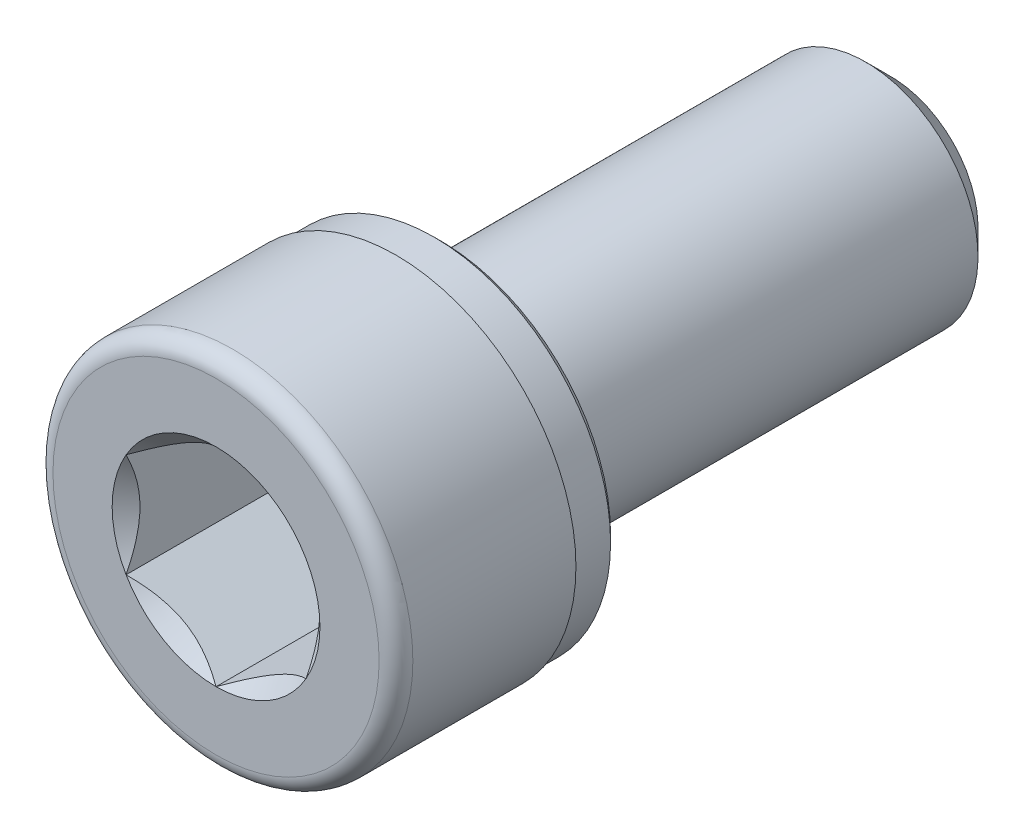
SolidWorks part; units mm, degrees
ref_plane "Front Plane" through (0, 0, 0) normal (0, 0, 1) x (1, 0, 0)
ref_plane "Top Plane" through (0, 0, 0) normal (0, 1, 0) x (1, 0, 0)
ref_plane "Right Plane" through (0, 0, 0) normal (1, 0, 0) x (0, 0, -1)
sketch "Sketch1" plane through (0, 0, 0) normal (1, 0, 0) x (0, 0, -1)
  line L0 (-15, 0) -> (15, 0) construction
  line L1 (15, 0) -> (15, 5)
  line L2 (15, 5) -> (-5, 5)
  line L3 (-5, 5) -> (-5, 8)
  line L4 (-5, 8) -> (-15, 8)
  line L5 (-15, 8) -> (-15, 0)
  line L6 (14.9062, 5.1624) -> (15.6562, 3.8633) construction
  line L7 (15.6562, 3.8633) -> (16.4062, 5.1624) construction
  line L8 (16.4062, 5.1624) -> (14.9062, 5.1624) construction
  line L9 (15, 5) -> (16.3125, 5) construction
  line L10 (15.6562, 5.1624) -> (15.6562, 5) construction
  line L11 (15.6562, 5) -> (15.6562, 4.0257) construction
  line L12 (15.6562, 4.0257) -> (15.6562, 3.8633) construction
  line L13 (15.5625, 4.0257) -> (15.75, 4.0257)
  line L14 (14.9531, 5.0812) -> (16.3594, 5.0812)
  line L15 (15.75, 4.0257) -> (16.3594, 5.0812)
  line L16 (15.5625, 4.0257) -> (14.9531, 5.0812)
  line L18 (-15, 4.6188) -> (-19, 2.3094)
  line L19 (-19, 2.3094) -> (-19, -2.3094)
  line L20 (-19, -2.3094) -> (-15, -4.6188)
  line L21 (-15, -4.6188) -> (-11, -2.3094)
  line L22 (-11, -2.3094) -> (-11, 2.3094)
  line L23 (-11, 2.3094) -> (-15, 4.6188)
  circle A0 centre (-15, 0) radius 4 construction
  circle A2 centre (-5, 5.9) radius 0.9
  point P5 (-7, 8)
  point P10 (11.25, 5)
  point P20 (15.6562, 5.0812)
  point P21 (-7.5, 0)
  point P22 (11.25, -5)
  dimension "Screw Size" = 10
  dimension "Head Diameter" = 16
  dimension "Head Height" = 10
  dimension "Length" = 20
  dimension "D1" = 2
  dimension "Pitch" = 1.5
  dimension "D3" = 0.1875
  dimension "D2" = 3.75
  dimension "Drive Size" = 8
  dimension "D4" = 7.5
  dimension "D5" = 13.6
sketch "Sketch2" plane through (0, 0, 0) normal (1, 0, 0) x (0, 0, -1)
  line L0 (-15, 8) -> (-15, 0) construction
  line L1 (-5, 8) -> (-15, 8) construction
  line L2 (-5, 5) -> (-5, 8) construction
  line L3 (15, 5) -> (-5, 5) construction
  line L4 (15, 0) -> (15, 5) construction
  line L5 (-15, 8) -> (-15, 0)
  line L6 (-5, 8) -> (-15, 8)
  line L7 (-5, 5) -> (-5, 8)
  line L8 (15, 5) -> (-5, 5)
  line L9 (15, 0) -> (15, 5)
  line L10 (-15, 0) -> (15, 0)
revolve "Revolve1" add sketch "Sketch2" angle 360 about L10
chamfer "Chamfer1" distance 1.125 angle 45 1 edges at (0, -5, -15)
sketch "Sketch3" plane through (0, 0, 5) normal (0, 0, -1) x (-1, 0, 0)
  circle A0 centre (0, 0) radius 7.84
  circle A1 centre (0, 0) radius 8 construction
  dimension "D1" = 0.16
extrude "Cut-Extrude1" cut sketch "Sketch3" against normal up to vertex (2 mm away) flip side to cut up to point (0, 8, 7)
chamfer "Chamfer2" distance 0.3 angle 45 1 edges at (-7.84, 0, 5)
fillet "Fillet1" radius 0.75 1 edges at (0, -8, 15)
sketch "Sketch4" plane through (0, 0, 0) normal (1, 0, 0) x (0, 0, -1)
  circle A0 centre (-5, 5.9) radius 0.9 construction
  circle A1 centre (-5, 5.9) radius 0.9
revolve "Revolve2" add sketch "Sketch4" angle 360 about L0
sketch "Sketch14" plane through (0, 0, 0) normal (1, 0, 0) x (0, 0, -1)
  circle A0 centre (-5, 5.9) radius 0.9 construction
  circle A1 centre (-5, 5.9) radius 0.9
revolve "Cut-Revolve1" cut sketch "Sketch14" angle 360 about L0
sketch "Sketch5" plane through (0, 0, 15) normal (0, 0, 1) x (1, 0, 0)
  line L1 (0, 4.6188) -> (-4, 2.3094)
  line L2 (-4, 2.3094) -> (-4, -2.3094)
  line L3 (-4, -2.3094) -> (0, -4.6188)
  line L4 (0, -4.6188) -> (4, -2.3094)
  line L5 (4, -2.3094) -> (4, 2.3094)
  line L6 (4, 2.3094) -> (0, 4.6188)
  circle A0 centre (0, 0) radius 4 construction
extrude "Cut-Extrude2" cut sketch "Sketch5" against normal up to vertex (7.5 mm away) up to point (0, 0, 7.5)
sketch "Sketch6" plane through (0, 0, 15) normal (0, 0, 1) x (1, 0, 0)
  circle A0 centre (0, 0) radius 4.6188
extrude "Cut-Extrude3" cut sketch "Sketch6" against normal blind 2.54 draft 45
split "Split1" [suppressed] bodies to split 138
sketch "Sketch7" [suppressed] plane through (0, 0, -15) normal (0, 0, -1) x (-1, 0, 0)
  circle A0 centre (0, 0) radius 5 construction
  circle A1 centre (0, 0) radius 5
curve "Helix/Spiral1" [suppressed] pitch 1.5 height 21.5 turns 14.3333
sketch "Sketch8" [suppressed] plane through (0, 0, 0) normal (1, 0, 0) x (0, 0, -1)
  line L0 (15.5625, 4.0257) -> (15.75, 4.0257) construction
  line L1 (15.5625, 4.0257) -> (14.9531, 5.0812) construction
  line L2 (14.9531, 5.0812) -> (16.3594, 5.0812) construction
  line L3 (15.75, 4.0257) -> (16.3594, 5.0812) construction
  line L4 (15.5625, 4.0257) -> (15.75, 4.0257)
  line L5 (15.5625, 4.0257) -> (14.9531, 5.0812)
  line L6 (14.9531, 5.0812) -> (16.3594, 5.0812)
  line L7 (15.75, 4.0257) -> (16.3594, 5.0812)
sweep "Cut-Sweep1" [suppressed] cut profiles "Sketch8" path "Helix/Spiral1"
sketch "Sketch9" [suppressed] plane through (0, 0, 5) normal (0, 0, -1) x (-1, 0, 0)
  circle A2 centre (0, 0) radius 5
extrude "Boss-Extrude1" [suppressed] add sketch "Sketch9" along normal blind 2.54 draft 45
sketch "Sketch12" [suppressed] plane through (0, 0, 7) normal (0, 0, -1) x (-1, 0, 0)
  line L0 (-0.0924, 8) -> (0, 7.84)
  line L1 (0, 8) -> (0, 0) construction
  line L2 (0, 7.84) -> (0.0924, 8)
  line L3 (0.0924, 8) -> (-0.0924, 8)
  line L4 (0, 8) -> (0, 7.84) construction
  circle A0 centre (0, 0) radius 7.84 construction
  dimension "D1" = 60
  dimension "D2" = 0.1848
sketch "Sketch13" [suppressed] plane through (0, 0, 0) normal (1, 0, 0) x (0, 0, -1)
  line L0 (-7, 7.84) -> (-11, 7.84)
  arc A0 (-15, 8) -> (-11, 7.84) centre (-11, 57.92) ccw
sweep "Cut-Sweep3" [suppressed] cut profiles "Sketch12" path "Sketch13"
pattern_circular "CirPattern2" [suppressed] count 68 over 360 about axis through (0, 0, 15) along (0, 0, -1) reverse direction yes of bodies 147
equation "\"D1@Sketch1\"=\"Head Height@Sketch1\"*1/5"
equation "\"D3@Sketch1\" = \"Pitch@Sketch1\" / 8"
equation "\"D2@Sketch1\"=\"Pitch@Sketch1\"*2.5"
equation "\"D4@Sketch1\"=\"Head Height@Sketch1\"*0.75"
equation "\"D1@Chamfer1\"=\"pitch@sketch1\"*0.75"
equation "\"D5@Sketch1\"=\"Head Diameter@Sketch1\"*0.85"
equation "\"D1@Chamfer2\" = \"Head Height@Sketch1\" * 0.03"
equation "\"D1@Fillet1\" = \"Head Height@Sketch1\" * 0.075"
equation "\"D3@Helix/Spiral1\" = \"Length@Sketch1\" + \"Pitch@Sketch1\""
equation "\"D4@Helix/Spiral1\"=\"pitch@sketch1\""
equation "\"D1@Fillet2\"=\"head height@sketch1\"*0.075"
equation "\"D1@CirPattern2\"=\"Head Diameter@Sketch1\" * 3.14 / \"D2@Sketch12\" * 0.25"
equation "\"D1@Sketch3\"=\"Head Diameter@Sketch1\"*0.01"
